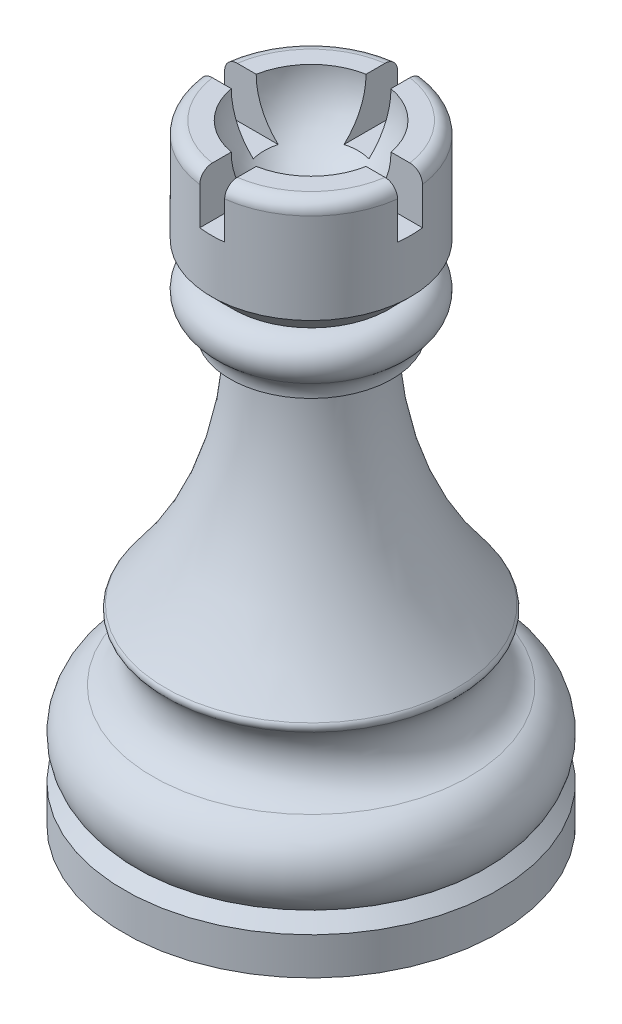
SolidWorks part; units mm, degrees
ref_plane "Front Plane" through (0, 0, 0) normal (0, 0, 1) x (1, 0, 0)
ref_plane "Top Plane" through (0, 0, 0) normal (0, 1, 0) x (1, 0, 0)
ref_plane "Right Plane" through (0, 0, 0) normal (1, 0, 0) x (0, 0, -1)
sketch "Sketch1" plane through (0, 0, 0) normal (1, 0, 0) x (0, 0, -1)
  line L0 (0, 0) -> (0, 43.5)
  line L1 (0, 0) -> (15, 0)
  line L2 (15, 0) -> (15, 3)
  line L3 (15, 3) -> (14, 4)
  line L4 (5, 34) -> (6.5, 34.2645)
  line L5 (5, 34) -> (0, 34) construction
  line L6 (6.2597, 39) -> (8, 40.7403)
  line L7 (8, 40.7403) -> (8, 48)
  line L8 (7, 49) -> (5.5, 49)
  arc A0 (14, 4) -> (12.7037, 9.736) centre (11.5, 6.4495) ccw
  arc A1 (11.6441, 14.7038) -> (12.7037, 9.736) centre (13.7355, 12.553) ccw
  arc A2 (5, 34) -> (11.6814, 15.3801) centre (34.2857, 34) ccw
  arc A3 (7.3021, 35.866) -> (6.5, 34.2645) centre (8.5, 34.2645) ccw
  arc A4 (7.3021, 35.866) -> (6.2597, 39) centre (6.2597, 37.2597) ccw
  arc A5 (8, 48) -> (7, 49) centre (7, 48) ccw
  arc A6 (0, 43.5) -> (5.5, 49) centre (0, 49) ccw
  arc A7 (11.6441, 14.7038) -> (11.6814, 15.3801) centre (11.2955, 15.0622) ccw
  point P7 (6.5, 34.2645)
  point P10 (0, 15)
  point P11 (12, 15)
  point P12 (5, 34)
  point P14 (15, 6.4495)
  point P24 (7.3021, 35.866)
  point P25 (8, 37.2597)
  point P26 (6.2597, 39)
  point P35 (12, 15)
  dimension "D6" = 3.5
  dimension "D15" = 2
  dimension "D16" = 4
  dimension "D17" = 1.5
  dimension "D18" = 5.5
  dimension "D20" = 3
  dimension "D22" = 0.5
  dimension "D1" = 49
  dimension "D2" = 15
  dimension "D3" = 3
  dimension "D4" = 1
  dimension "D5" = 45
  dimension "D7" = 15
  dimension "D8" = 5
  dimension "D9" = 34
  dimension "D10" = 6.5
  dimension "D11" = 10
  dimension "D12" = 8
  dimension "D13" = 39
  dimension "D14" = 45
  dimension "D19" = 43.5
  dimension "D21" = 12
revolve "Revolve2" add sketch "Sketch1" angle 360 about L0
sketch "Sketch2" plane through (0, 0, 0) normal (1, 0, 0) x (0, 0, -1)
  line L0 (5.5, 49) -> (-5.5, 49) construction
  line L1 (-1, 49) -> (1, 49)
  line L2 (-1, 49) -> (-1, 45)
  line L3 (-1, 45) -> (1, 45)
  line L4 (1, 49) -> (1, 45)
  line L5 (0, 49) -> (0, 51.7203) construction
  dimension "D1" = 4
  dimension "D2" = 2
extrude "Cut-Extrude1" cut sketch "Sketch2" against normal blind 10 and the other way blind 10
sketch "Sketch3" plane through (0, 0, 0) normal (0, 0, 1) x (1, 0, 0)
  line L0 (0, 0) -> (0, 4) construction
  line L1 (6.9282, 49) -> (-6.9282, 49) construction
  line L2 (-1, 49) -> (1, 49)
  line L3 (-1, 49) -> (-1, 45)
  line L4 (-1, 45) -> (1, 45)
  line L5 (1, 49) -> (1, 45)
  dimension "D1" = 4
  dimension "D2" = 2
extrude "Cut-Extrude2" cut sketch "Sketch3" against normal blind 10 and the other way blind 10
